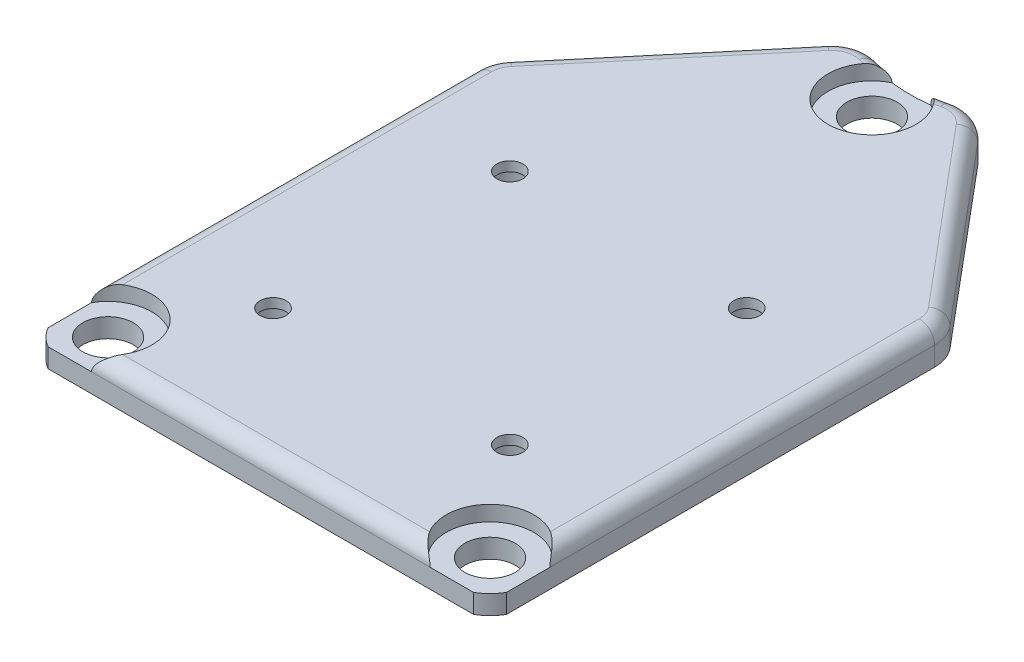
SolidWorks part; units mm, degrees
ref_plane "Front Plane" through (0, 0, 0) normal (0, 0, 1) x (1, 0, 0)
ref_plane "Top Plane" through (0, 0, 0) normal (0, 1, 0) x (1, 0, 0)
ref_plane "Right Plane" through (0, 0, 0) normal (1, 0, 0) x (0, 0, -1)
sketch "Sketch1" plane through (0, 0, 0) normal (0, 1, 0) x (1, 0, 0)
  line L0 (0, 0) -> (0, -72.4) construction
  circle A0 centre (0, -72.4) radius 6.3405 construction
  point P4 (25, -100)
  point P7 (-25, -100)
  point P17 (0, -25)
  dimension "D1" = 72.4
  dimension "D2" = 25
  dimension "D3" = 100
  dimension "D5" = 25
sketch "Sketch2" plane through (0, 0, 0) normal (0, 1, 0) x (1, 0, 0)
  line L0 (-30, -45) -> (-7.7214, -18.4494)
  line L6 (0, 0) -> (0, -72.4) construction
  line L7 (0, -75) -> (0, -52.0117) construction
  line L9 (-30, -105) -> (30, -105)
  line L10 (-30, -105) -> (-30, -45)
  line L12 (30, -105) -> (30, -45)
  line L13 (-30, -105) -> (30, -45) construction
  line L14 (-30, -45) -> (30, -105) construction
  line L15 (7.7214, -18.4494) -> (30, -45)
  arc A0 (-7.7214, -18.4494) -> (7.7214, -18.4494) centre (0, 0) ccw
  point P14 (0, -75)
  point P15 (0, -75)
  dimension "D5" = 220
  dimension "D6" = 220
  dimension "D2" = 20
  dimension "D1" = 25
  dimension "D3" = 60
  dimension "D4" = 60
extrude "Boss-Extrude1" add sketch "Sketch2" along normal blind 4.5 contours L10 L0 A0 L15 L12 L9
hole_wizard "Hole1" positions "Sketch3" profile "Sketch4" legacy end condition up to next
sketch "Sketch3" plane through (0, 4.5, 0) normal (0, 1, 0) x (1, 0, 0)
  point P4 (-25, -100)
  point P6 (25, -100)
  point P14 (0, -25)
sketch "Sketch4" plane through (-25, 4.5, 100) normal (1, 0, 0) x (0, 0, 1)
  line L0 (0, 0) -> (0, 4.5)
  line L1 (0, 4.5) -> (3.3, 4.5)
  line L3 (3.3, 4.5) -> (3.3, 2)
  line L4 (3.3, 2) -> (5.75, 2)
  line L5 (5.75, 2) -> (5.75, 0)
  line L7 (5.75, 0) -> (0, 0)
  line L11 (0, -6.35) -> (0, 107.95) construction
  dimension "Thru Hole Dia." = 6.6
  dimension "Thru Hole Depth" = 4.5
  dimension "C'Bore Dia." = 11.5
  dimension "C'Bore Depth" = 2
sketch "Sketch5" plane through (0, 4.5, 0) normal (0, 1, 0) x (1, 0, 0)
  line L0 (-30, -105) -> (-27.8395, -105) construction
  line L5 (-30, -102.8395) -> (-30, -105)
  line L6 (-30, -105) -> (-27.8395, -105)
  line L11 (0, -105) -> (0, -90.3325) construction
  line L12 (-22.1605, -105) -> (22.1605, -105) construction
  line L13 (30, -105) -> (27.8395, -105)
  line L14 (30, -102.8395) -> (30, -105)
  arc A0 (-30, -102.8395) -> (-27.8395, -105) centre (-25, -100) ccw
  arc A1 (30, -102.8395) -> (27.8395, -105) centre (25, -100) cw
extrude "Cut-Extrude3" cut sketch "Sketch5" against normal through all
sketch "Sketch6" plane through (0, 0, 0) normal (0, -1, 0) x (1, 0, 0)
  line L0 (0, 0) -> (0, 72.4) construction
  point P0 (-15.5, 56.9)
  point P5 (0, 72.4)
  point P8 (-15.5, 87.9)
  point P9 (15.5, 87.9)
  point P10 (15.5, 56.9)
  point P11 (0, 72.4)
  dimension "D1" = 15.5
  dimension "D2" = 15.5
  dimension "D3" = 4
hole_wizard "CBORE for M3 SHCS1" positions "Sketch7" profile "Sketch8" counterbore size "M3" standard "ANSI Metric" end condition through all
sketch "Sketch7" plane through (0, 0, 0) normal (0, -1, 0) x (-1, 0, 0)
  point P0 (-15.5, -56.9)
  point P3 (15.5, -56.9)
  point P6 (15.5, -87.9)
  point P9 (-15.5, -87.9)
sketch "Sketch8" plane through (15.5, 0, 56.9) normal (1, 0, 0) x (0, 0, -1)
  line L0 (0, 0) -> (0, 4.5)
  line L1 (0, 4.5) -> (1.7, 4.5)
  line L3 (1.7, 4.5) -> (1.7, 3.25)
  line L4 (1.7, 3.25) -> (3.25, 3.25)
  line L5 (3.25, 3.25) -> (3.25, 0)
  line L7 (3.25, 0) -> (0, 0)
  line L11 (0, -6.35) -> (0, 107.95) construction
  dimension "Thru Hole Dia." = 3.4
  dimension "Thru Hole Depth" = 4.5
  dimension "C'Bore Dia." = 6.5
  dimension "C'Bore Depth" = 3.25
fillet "Fillet4" radius 5 4 edges at (-30, 2.25, 45) (-7.7214, 2.25, 18.4494) (7.7214, 2.25, 18.4494) (30, 2.25, 45)
fillet "Fillet3" radius 2 11 edges at (30, 4.5, 71.9902) (0, 4.5, 105) (-30, 4.5, 71.9902) (-19.3624, 4.5, 32.3226) (-29.6985, 4.5, 45.1098) (-3.6995, 4.5, 19.6549) (-7.6079, 4.5, 19.4975) (29.6985, 4.5, 45.1098) (19.3624, 4.5, 32.3226) (7.6079, 4.5, 19.4975) (3.6995, 4.5, 19.6549)
